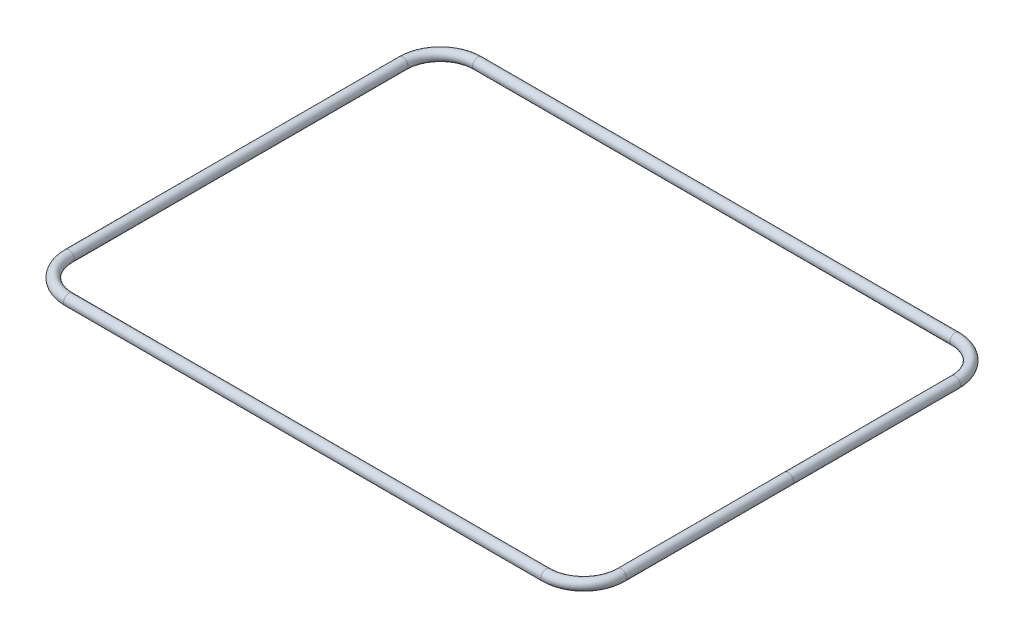
SolidWorks part; units mm, degrees
ref_plane "Front Plane" through (0, 0, 0) normal (0, 0, 1) x (1, 0, 0)
ref_plane "Top Plane" through (0, 0, 0) normal (0, 1, 0) x (1, 0, 0)
ref_plane "Right Plane" through (0, 0, 0) normal (1, 0, 0) x (0, 0, -1)
sketch "BaseDimensions" plane through (0, 0, 0) normal (0, 1, 0) x (1, 0, 0)
  line L0 (0, -76.2) -> (0, 76.2) construction
  line L1 (101.6, 0) -> (-101.6, 0) construction
  point P5 (0, 0)
  point P6 (0, 0)
  dimension "D1" = 152.4
  dimension "D2" = 203.2
sketch "O-RingPath" plane through (0, 0, 0) normal (0, 1, 0) x (1, 0, 0)
  line L0 (80.6713, -69.1388) -> (-80.6713, -69.1388)
  line L1 (93.3713, -56.4388) -> (93.3713, 56.4388)
  line L2 (0, 0) -> (0, -69.1388) construction
  line L3 (93.3713, 0) -> (0, 0) construction
  line L4 (-93.3713, -56.4388) -> (-93.3713, 56.4388)
  line L5 (80.6713, 69.1388) -> (-80.6713, 69.1388)
  arc A0 (80.6713, -69.1388) -> (93.3713, -56.4388) centre (80.6713, -56.4388) ccw
  arc A1 (-80.6713, -69.1388) -> (-93.3713, -56.4388) centre (-80.6713, -56.4388) cw
  arc A2 (-80.6713, 69.1388) -> (-93.3713, 56.4388) centre (-80.6713, 56.4388) ccw
  arc A3 (80.6713, 69.1388) -> (93.3713, 56.4388) centre (80.6713, 56.4388) cw
  point P17 (-93.3713, 0)
  dimension "D2" = 12.7
  dimension "D3" = 7.0612
sketch "O-RingProfile" plane through (0, 0, 0) normal (0, 0, 1) x (1, 0, 0)
  circle A0 centre (93.3713, 0) radius 1.7653
  dimension "D1" = 3.5306
sweep "Sweep2" add profiles "O-RingProfile" path "O-RingPath"
ref_plane "TopOfRing" through (0, 1.7653, 0) normal (0, 1, 0) x (1, 0, 0)
ref_plane "BottomOfRing" through (0, -1.7653, 0) normal (0, -1, 0) x (-1, 0, 0)
equation "\"D1@O-RingProfile\" = \"O-Ring_CS@BladderAssembly.Assembly\""
equation "\"D1@BaseDimensions\"=\"BaseWidth@BladderAssembly.Assembly\""
equation "\"D2@BaseDimensions\"=\"BaseLength@BladderAssembly.Assembly\""
equation "\"O_Ring_Len\"= \"O-Ring_Len@BladderAssembly.Assembly\""
equation "\"D1@O-RingPath\"=\"O_Ring_Len\""
